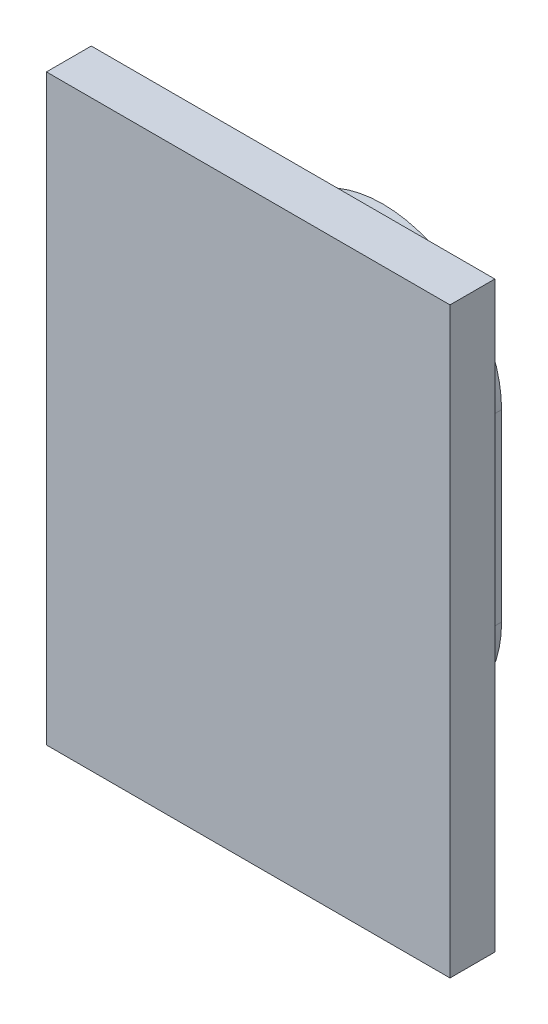
SolidWorks part; units mm, degrees
ref_plane "Front Plane" through (0, 0, 0) normal (0, 0, 1) x (1, 0, 0)
ref_plane "Top Plane" through (0, 0, 0) normal (0, 1, 0) x (1, 0, 0)
ref_plane "Right Plane" through (0, 0, 0) normal (1, 0, 0) x (0, 0, -1)
sketch "Sketch1" plane through (0, 0, 0) normal (0, 0, 1) x (1, 0, 0)
  line L1 (-19.6138, 16.2133) -> (25.3862, 16.2133)
  line L2 (-19.6138, 16.2133) -> (-19.6138, -48.7867)
  line L3 (-19.6138, -48.7867) -> (25.3862, -48.7867)
  line L4 (25.3862, 16.2133) -> (25.3862, -48.7867)
  dimension "D1" = 45
  dimension "D2" = 65
extrude "Boss-Extrude1" add sketch "Sketch1" along normal blind 5
sketch "Sketch4" plane through (0, 0, 0) normal (0, 0, -1) x (-1, 0, 0)
  line L0 (-2.8862, -28.7867) -> (-2.8862, 49971.2133) construction
  line L3 (19.6138, -48.7867) -> (-25.3862, -48.7867) construction
  line L4 (-15.3862, -16.2867) -> (49984.6138, -16.2867) construction
  line L5 (-25.3862, -48.7867) -> (-25.3862, 16.2133) construction
  line L6 (-2.8862, -6.0367) -> (-2.8862, -26.5367) construction
  line L7 (10.3638, -6.0367) -> (10.3638, -26.5367)
  line L8 (-16.1362, -6.0367) -> (-16.1362, -26.5367)
  line L9 (7.8638, -6.0367) -> (7.8638, -26.5367)
  line L10 (-13.6362, -6.0367) -> (-13.6362, -26.5367)
  arc A0 (10.3638, -6.0367) -> (-16.1362, -6.0367) centre (-2.8862, -6.0367) ccw
  arc A1 (-16.1362, -26.5367) -> (10.3638, -26.5367) centre (-2.8862, -26.5367) ccw
  arc A2 (-13.6362, -26.5367) -> (7.8638, -26.5367) centre (-2.8862, -26.5367) ccw
  arc A3 (7.8638, -6.0367) -> (-13.6362, -6.0367) centre (-2.8862, -6.0367) ccw
  point P4 (-2.8862, -48.7867)
  point P9 (-25.3862, -16.2867)
  point P12 (-2.8862, -16.2867)
  dimension "D1" = 2.5
extrude "Boss-Extrude2" add sketch "Sketch4" along normal blind 10
